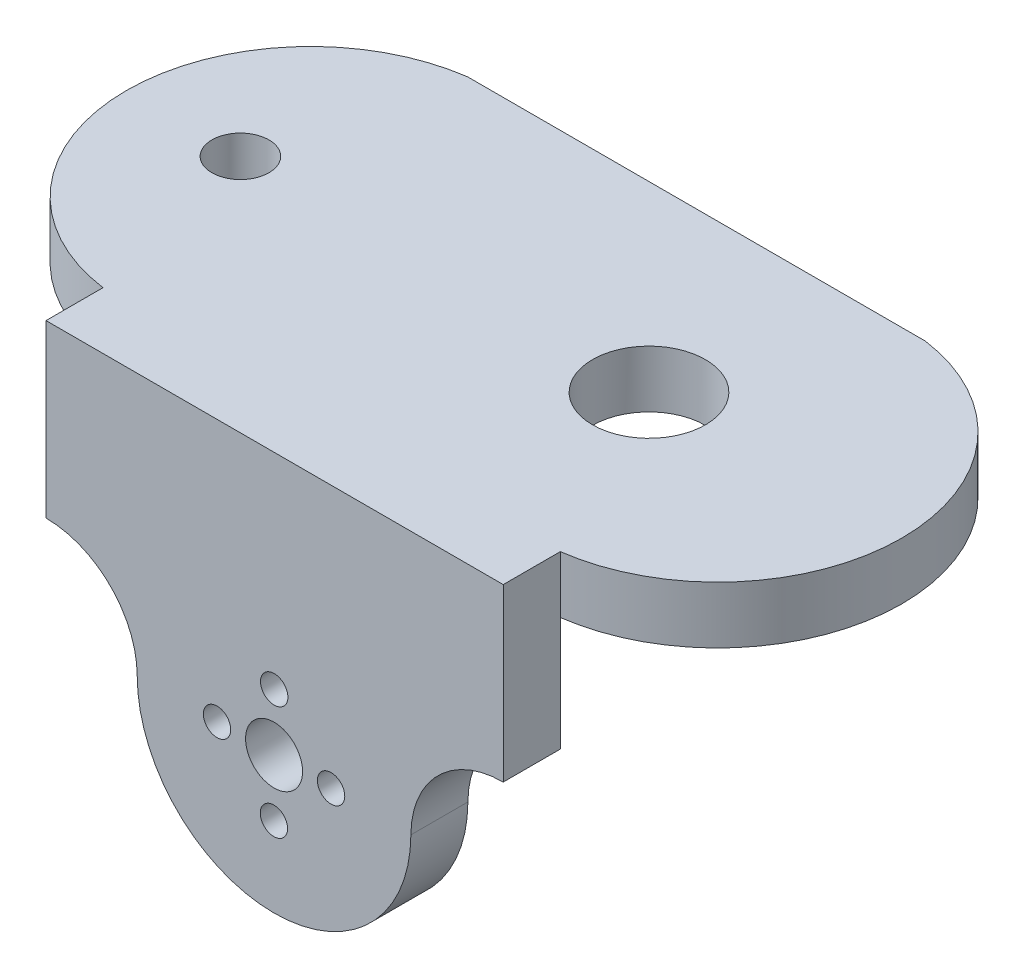
SolidWorks part; units mm, degrees
material "1060 Alloy"
ref_plane "Front" through (0, 0, 0) normal (0, 0, 1) x (1, 0, 0)
ref_plane "Top" through (0, 0, 0) normal (0, 1, 0) x (1, 0, 0)
ref_plane "Right" through (0, 0, 0) normal (1, 0, 0) x (0, 0, -1)
sketch "Sketch1" plane through (0, 0, 0) normal (0, 0, 1) x (1, 0, 0)
  line L1 (0, 0) -> (40.1, 0)
  line L2 (0, 0) -> (0, -10)
  line L3 (0, -10) -> (40.1, -10)
  line L4 (40.1, 0) -> (40.1, -10)
  arc A0 (0, -10) -> (8, -18) centre (0, -18) cw
  arc A1 (8, -18) -> (31.9999, -18.0599) centre (20, -18) ccw
  arc A2 (31.9999, -18.0599) -> (40.1, -10) centre (40.1, -18.1003) cw
  dimension "D3" = 8
  dimension "D4" = 12
  dimension "D1" = 40.1
  dimension "D2" = 10
extrude "Boss-Extrude1" add sketch "Sketch1" along normal blind 5 contours L4 L1 L2 L3 | A1 A2 L3 A0 region at (20.05, -5, 0) region at (20.0114, -18.4742, 0)
sketch "Sketch2" plane through (0, 0, 5) normal (0, 0, 1) x (1, 0, 0)
  line L0 (40.1, 0) -> (40.1, -10) construction
  line L1 (0, 0) -> (40.1, 0)
  line L2 (0, 0) -> (0, 5)
  line L3 (0, 5) -> (40.1, 5)
  line L4 (40.1, 0) -> (40.1, 5)
  dimension "D1" = 5
extrude "Boss-Extrude2" add sketch "Sketch2" against normal blind 37
sketch "Sketch3" plane through (0, 5, 0) normal (0, 1, 0) x (1, 0, 0)
  line L0 (0, 32) -> (0, 0) construction
  line L1 (0, 32) -> (0, 0)
  line L4 (20.05, 32) -> (20.05, -5) construction
  line L5 (40.1, 32) -> (0, 32) construction
  line L6 (40.1, -5) -> (0, -5) construction
  line L7 (40.1, 32) -> (40.1, 0)
  arc A0 (0, 0) -> (0, 32) centre (2.2006, 16) cw
  arc A2 (40.1, 0) -> (40.1, 32) centre (37.8994, 16) ccw
  point P9 (-13.95, 16)
  dimension "D1" = 34
extrude "Boss-Extrude3" add sketch "Sketch3" against normal up to surface (5 mm away) up to face at (20.05, 0, -16)
sketch "Sketch4" plane through (0, 0, 5) normal (0, 0, 1) x (1, 0, 0)
  line L0 (20.0299, -6) -> (19.9701, -30) construction
  line L1 (8.0001, -17.9401) -> (31.9999, -18.0599) construction
  arc A0 (8, -18) -> (31.9999, -18.0599) centre (20, -18) ccw construction
  arc A1 (8, -18) -> (31.9999, -18.0599) centre (20, -18) ccw
  circle A2 centre (20, -18) radius 2.5
  circle A3 centre (20.0125, -13) radius 1.2
  circle A4 centre (15, -17.9751) radius 1.2
  circle A5 centre (19.9875, -23) radius 1.2
  circle A6 centre (25, -18.0249) radius 1.2
  point P7 (20, -18)
  point P10 (20, -18)
  dimension "D1" = 5
  dimension "D2" = 2.4
  dimension "D3" = 5
  dimension "D4" = 5
  dimension "D5" = 5
  dimension "D6" = 5
extrude "Cut-Extrude1" cut sketch "Sketch4" against normal through all contours A3 | A2 | A4 | A5 | A6 region at (20, -18, 5) region at (20.0125, -13, 5) region at (15, -17.9751, 5) region at (19.9875, -23, 5) region at (25, -18.0249, 5)
sketch "Sketch5" plane through (0, 5, 0) normal (0, 1, 0) x (1, 0, 0)
  line L0 (-13.95, 16) -> (54.05, 16) construction
  arc A0 (40.1, 0) -> (40.1, 32) centre (37.8994, 16) ccw construction
  arc A1 (0, 32) -> (0, 0) centre (2.2006, 16) ccw construction
  arc A2 (40.1, 0) -> (40.1, 32) centre (37.8994, 16) ccw
  arc A3 (0, 32) -> (0, 0) centre (2.2006, 16) ccw
  circle A4 centre (31.88, 16) radius 4.955
  circle A7 centre (-3.95, 16) radius 2.5
  dimension "D2" = 9.91
  dimension "D3" = 35.83
  dimension "D1" = 5
  dimension "D4" = 10
extrude "Cut-Extrude2" cut sketch "Sketch5" against normal through all contours A4 | A4 | A7 region at (31.88, 5, -16)
